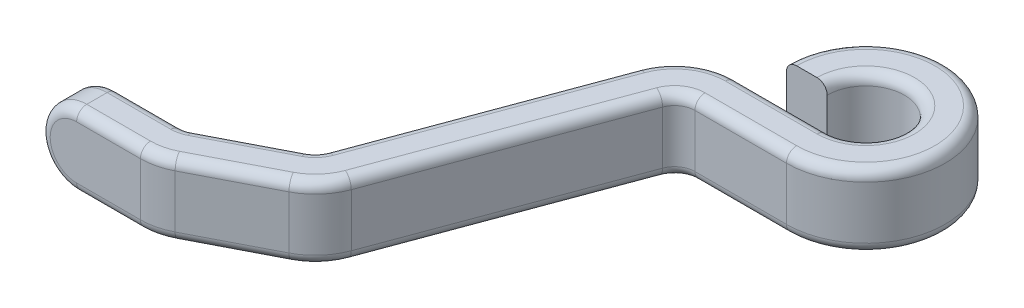
SolidWorks part; units mm, degrees
ref_plane "Front" through (0, 0, 0) normal (0, 0, 1) x (1, 0, 0)
ref_plane "Top" through (0, 0, 0) normal (0, 1, 0) x (1, 0, 0)
ref_plane "Right" through (0, 0, 0) normal (1, 0, 0) x (0, 0, -1)
sketch "Sketch1" plane through (0, 0, 0) normal (0, 0, 1) x (1, 0, 0)
  line L0 (5.3053, 0.9) -> (3.996, 0.9)
  line L1 (5.3053, -0.9) -> (5.3053, 0.9)
  line L2 (3.996, -0.9) -> (5.3053, -0.9)
  line L5 (5.3093, 0.95) -> (3.996, 0.95) construction
  line L6 (5.4053, -1.0222) -> (5.4053, 1.0222) construction
  line L8 (3.996, -0.95) -> (5.3093, -0.95) construction
  arc A0 (3.996, 0.9) -> (3.996, -0.9) centre (3.996, 0) ccw
  arc A2 (3.996, 0.95) -> (3.996, -0.95) centre (3.996, 0) ccw construction
  arc A22 (5.3093, 0.95) -> (5.4053, 1.0222) centre (5.3093, 1.05) ccw construction
  arc A24 (5.4053, -1.0222) -> (5.3093, -0.95) centre (5.3093, -1.05) ccw construction
extrude "Base-Extrude" add sketch "Sketch1" along normal blind 1
sketch "Sketch2" plane through (0, 0, 0) normal (0, 1, 0) x (1, 0, 0)
  line L0 (5.3053, -1) -> (5.3053, 0) construction
  line L1 (5.3053, -1) -> (5.3053, 0) construction
  line L2 (13.6003, 8.7927) -> (7.5184, 8.7927) construction
  line L3 (13.6003, 8.7927) -> (13.6003, 3.4625) construction
  line L4 (13.6003, 7.3427) -> (11.3503, 7.3427)
  line L5 (5.3053, -0.5) -> (5.5625, -0.5)
  line L6 (10.4125, 6.6898) -> (8.3456, 1.1052)
  line L7 (6.0211, -0.3886) -> (7.8664, 0.5637)
  arc A0 (7.8664, 0.5637) -> (8.3456, 1.1052) centre (7.4078, 1.4523) ccw
  circle A2 centre (13.6003, 8.7927) radius 0.95 construction
  arc A3 (13.6003, 7.3427) -> (12.1503, 8.7927) centre (13.6003, 8.7927) ccw
  arc A4 (6.0211, -0.3886) -> (5.5625, -0.5) centre (5.5625, 0.5) cw
  arc A5 (10.4125, 6.6898) -> (11.3503, 7.3427) centre (11.3503, 6.3427) cw
sketch "Sketch3" plane through (5.3053, 0, 0) normal (1, 0, 0) x (0, 0, -1)
  line L4 (0, -0.9) -> (0, 0.9)
  line L5 (0, 0.9) -> (-1, 0.9)
  line L6 (-1, 0.9) -> (-1, -0.9)
  line L7 (-1, -0.9) -> (0, -0.9)
  line L8 (0, -0.9) -> (0, 0.9)
  line L9 (0, 0.9) -> (-1, 0.9)
  line L10 (-1, 0.9) -> (-1, -0.9)
  line L11 (-1, -0.9) -> (0, -0.9)
  dimension "D1" = 0
sweep "Boss-Sweep1" add profiles "Sketch3" path "Sketch2"
fillet "Fillet2" radius 0.25 17 edges at (14.9792, -0.9, -10.1715) (12.4753, -0.9, -6.8427) (11.0646, -0.9, -6.753) (9.848, -0.9, -3.7239) (4.7793, -0.9, 1) (3.096, 0, 1) (14.9792, 0.9, -10.1715) (4.7793, 0.9, 1) (12.4753, 0.9, -6.8427) (11.0646, 0.9, -6.753) (9.848, 0.9, -3.7239) (8.5311, -0.9, -0.4582) (7.173, -0.9, 0.3568) (5.9164, -0.9, 0.9576) (5.9164, 0.9, 0.9576) (7.173, 0.9, 0.3568) (8.5311, 0.9, -0.4582)
fillet "Fillet3" radius 0.25 17 edges at (14.2721, -0.9, -9.4644) (12.4753, -0.9, -7.8427) (10.4933, -0.9, -7.5737) (8.9101, -0.9, -4.071) (4.7793, -0.9, 0) (3.096, 0, 0) (14.2721, 0.9, -9.4644) (4.7793, 0.9, 0) (12.4753, 0.9, -7.8427) (10.4933, 0.9, -7.5737) (8.9101, 0.9, -4.071) (7.7822, -0.9, -1.121) (6.7144, -0.9, -0.5318) (5.6805, -0.9, -0.0141) (5.6805, 0.9, -0.0141) (6.7144, 0.9, -0.5318) (7.7822, 0.9, -1.121)
shell "Shell3" [suppressed] thickness 0.1
